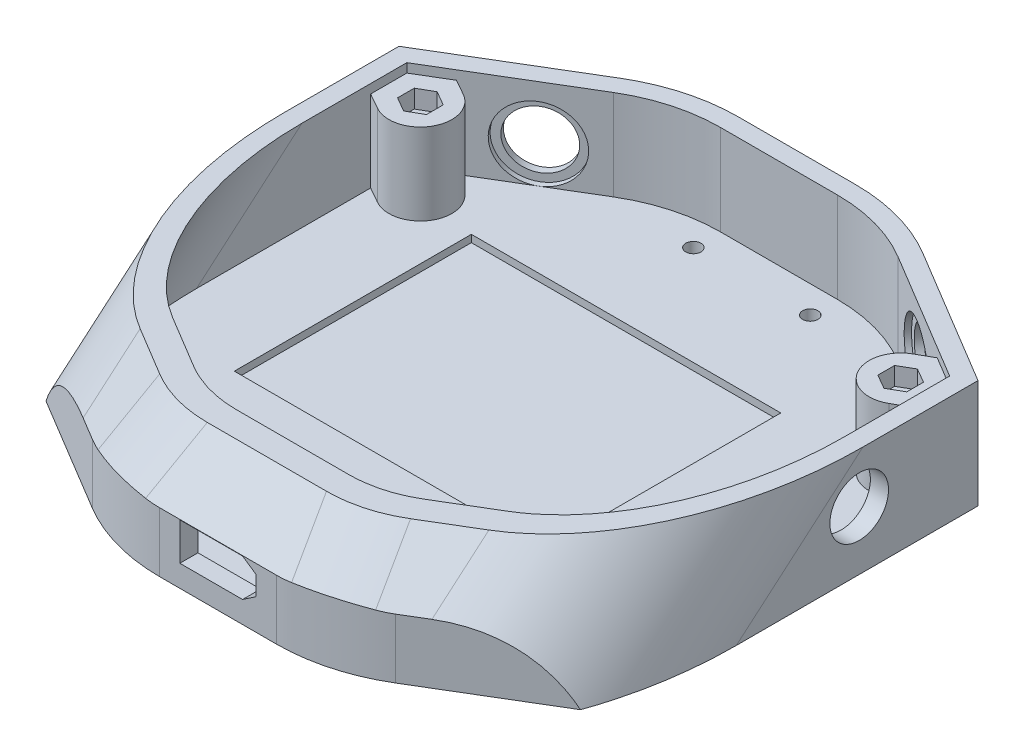
SolidWorks part; units mm, degrees
ref_plane "Front Plane" through (0, 0, 0) normal (0, 0, 1) x (1, 0, 0)
ref_plane "Top Plane" through (0, 0, 0) normal (0, 1, 0) x (1, 0, 0)
ref_plane "Right Plane" through (0, 0, 0) normal (1, 0, 0) x (0, 0, -1)
sketch "Sketch3" plane through (0, 0, 0) normal (0, 1, 0) x (1, 0, 0)
  line L0 (-80, 0) -> (80, 0) construction
  line L1 (80, 0) -> (80, -100)
  line L2 (80, -100) -> (30, -130)
  line L3 (30, -130) -> (-30, -130)
  line L4 (0, -130) -> (0, 0) construction
  line L5 (-80, -100) -> (-30, -130)
  line L6 (-80, 0) -> (-80, -100)
  line L7 (-80, 0) -> (-30, 30)
  line L8 (-30, 30) -> (30, 30)
  line L9 (30, 30) -> (80, 0)
  point P10 (0, 0)
  point P13 (0, 30)
  dimension "D1" = 80
  dimension "D2" = 100
  dimension "D3" = 30
  dimension "D4" = 30
  dimension "D5" = 30
extrude "Boss-Extrude1" add sketch "Sketch3" along normal blind 30
chamfer "Chamfer1" distance 13.5 angle 45 3 edges at (55, 30, 115) (0, 30, 130) (-55, 30, 115)
fillet "Fillet1" radius 50 6 edges at (30, 8.25, 130) (-80, 23.25, 92.1282) (80, 23.25, 92.1282) (28.1304, 23.25, 123.25) (-28.1304, 23.25, 123.25) (-30, 8.25, 130)
fillet "Fillet2" radius 50 2 edges at (-30, 15, -30) (30, 15, -30)
shell "Shell1" thickness 5 removed face at (0, 30, 45.3245)
sketch "Sketch4" plane through (0, 0, 130) normal (0, 0, 1) x (1, 0, 0)
  line L0 (16.1508, 16.5) -> (-16.1508, 16.5) construction
  line L1 (-10.3, 16.15) -> (6.7, 16.15) construction
  line L2 (6.7, 16.15) -> (10.3, 13.7) construction
  line L3 (10.3, 13.7) -> (10.3, 8.7) construction
  line L4 (10.3, 8.7) -> (6.7, 6.25) construction
  line L5 (6.7, 6.25) -> (-10.3, 6.25) construction
  line L6 (-10.3, 6.25) -> (-10.3, 16.15) construction
  line L7 (10.3, 11.2) -> (-10.3, 11.2) construction
  line L8 (10.55, 13.8323) -> (10.55, 8.5677)
  line L9 (10.55, 8.5677) -> (6.777, 6)
  line L10 (6.777, 6) -> (-10.55, 6)
  line L11 (-10.55, 6) -> (-10.55, 16.4)
  line L12 (-10.55, 16.4) -> (6.777, 16.4)
  line L13 (6.777, 16.4) -> (10.55, 13.8323)
  line L15 (-16.1508, 5) -> (16.1508, 5) construction
  point P14 (0, 11.2)
  point P15 (0, 16.5)
  dimension "D1" = 17
  dimension "D2" = 9.9
  dimension "D3" = 5
  dimension "D4" = 3.6
  dimension "D6" = 1
  dimension "D5" = 0.25
extrude "Cut-Extrude1" cut sketch "Sketch4" against normal up to next
sketch "Sketch5" plane through (0, 5, 0) normal (0, 1, 0) x (1, 0, 0)
  line L1 (-50, -10) -> (35.5, -10)
  line L2 (-50, -10) -> (-50, -75.5)
  line L3 (-50, -75.5) -> (35.5, -75.5)
  line L4 (35.5, -10) -> (35.5, -75.5)
  dimension "D1" = 85.5
  dimension "D2" = 65.5
  dimension "D3" = 50
  dimension "D4" = 10
extrude "Cut-Extrude2" cut sketch "Sketch5" against normal blind 2
sketch "Sketch6" plane through (21.1765, 0, -35.2941) normal (0.5145, 0, -0.8575) x (-0.8575, 0, -0.5145)
  line L2 (-39.2594, 15.1203) -> (-39.2594, 0) construction
  line L3 (-24.1391, 15.1203) -> (-39.2594, 15.1203) construction
  line L5 (-68.5994, 0) -> (-24.1391, 0) construction
  line L6 (-24.1391, 0) -> (-24.1391, 30) construction
  line L7 (-65.7685, 5) -> (-24.1391, 5) construction
  circle A0 centre (-39.2594, 15.1203) radius 10.1203
  dimension "D1" = 20.2406
extrude "Cut-Extrude3" cut sketch "Sketch6" against normal blind 1.488
sketch "Sketch7" plane through (18.604, 0, -31.0067) normal (-0.5145, 0, 0.8575) x (0.8575, 0, 0.5145)
  circle A1 centre (39.2594, 15.1203) radius 10.1203
  circle A2 centre (39.2594, 15.1203) radius 10.1203
  dimension "D2" = 0
extrude "Cut-Extrude4" cut sketch "Sketch7" against normal blind 1.488
sketch "Sketch8" plane through (21.1765, 0, -35.2941) normal (0.5145, 0, -0.8575) x (-0.8575, 0, -0.5145)
  circle A0 centre (-39.2594, 15.1203) radius 7.9375
  dimension "D1" = 15.875
extrude "Cut-Extrude5" cut sketch "Sketch8" against normal up to next
mirror "Mirror1" about plane through (0, 0, 0) normal (1, 0, 0) of "Cut-Extrude3", "Cut-Extrude4", "Cut-Extrude5"
sketch "Sketch9" plane through (0, 30, 0) normal (0, 1, 0) x (1, 0, 0)
  line L2 (-75, -2.831) -> (-66.4251, 2.314)
  line L3 (-39.3031, 18.5872) -> (-75, -2.831) construction
  line L4 (-75, -2.831) -> (-75, -60.9491) construction
  line L5 (-75, -2.831) -> (-75, -12.831)
  line L6 (-66.4251, 2.314) -> (-62.0741, -0.1495)
  line L7 (-70.649, -15.2944) -> (-75, -12.831)
  arc A1 (-62.0741, -0.1495) -> (-70.649, -15.2944) centre (-66.3615, -7.722) cw
  dimension "D1" = 10
  dimension "D2" = 10
  dimension "D3" = 5
extrude "Boss-Extrude2" add sketch "Sketch9" along normal offset from surface (22.5 mm away) 2.5 from surface up to face at (0, 30, 43.9845) starting at face at (0, 5, 44.5926)
sketch "Sketch10" plane through (0, 30, 0) normal (0, 1, 0) x (1, 0, 0)
  line L1 (-70.3615, -5.4126) -> (-70.3615, -10.0314)
  line L2 (-70.3615, -10.0314) -> (-66.3615, -12.3408)
  line L3 (-66.3615, -12.3408) -> (-62.3615, -10.0314)
  line L4 (-62.3615, -10.0314) -> (-62.3615, -5.4126)
  line L5 (-62.3615, -5.4126) -> (-66.3615, -3.1032)
  line L6 (-66.3615, -3.1032) -> (-70.3615, -5.4126)
  circle A0 centre (-66.3615, -7.722) radius 4 construction
  arc A2 (-70.649, -15.2944) -> (-62.0741, -0.1495) centre (-66.3615, -7.722) ccw construction
  dimension "D1" = 8
extrude "Cut-Extrude6" cut sketch "Sketch10" against normal blind 5 from surface contours L5 L6 L1 L2 L3 L4 region at (-66.3615, 30, 7.722) starting at face at (-68.3151, 27.5, 6.6159)
mirror "Mirror2" about plane through (0, 0, 0) normal (1, 0, 0) of "Boss-Extrude2", "Cut-Extrude6"
sketch "Sketch11" plane through (0, 5, 0) normal (0, 1, 0) x (1, 0, 0)
  line L1 (-50, -75.5) -> (35.5, -75.5) construction
  line L2 (-50, -75.5) -> (35.5, -75.5) construction
  line L3 (-7.25, -75.5) -> (-27.25, -75.5) construction
  circle A0 centre (-16.1508, 17.5) radius 2.1
  circle A1 centre (-27.25, -95.5) radius 2.1
  circle A3 centre (-16.1508, 17.5) radius 5 construction
  circle A4 centre (-27.25, -95.5) radius 5 construction
  dimension "D1" = 4.2
  dimension "D2" = 4.2
  dimension "D3" = 10
  dimension "D5" = 10
  dimension "D4" = 7.5
  dimension "D6" = 20
  dimension "D7" = 20
extrude "Cut-Extrude7" cut sketch "Sketch11" against normal through all
mirror "Mirror3" about plane through (0, 0, 0) normal (1, 0, 0) of "Cut-Extrude7"
sketch "Sketch12" plane through (80, 0, 0) normal (1, 0, 0) x (0, 0, -1)
  line L0 (0, 30) -> (0, 0) construction
  line L1 (-12.831, 27.5) -> (-12.831, 5) construction
  circle A0 centre (-32.831, 16.25) radius 8.1
  point P10 (-12.831, 16.25)
  dimension "D1" = 16.2
  dimension "D2" = 20
extrude "Cut-Extrude8" cut sketch "Sketch12" against normal up to next
